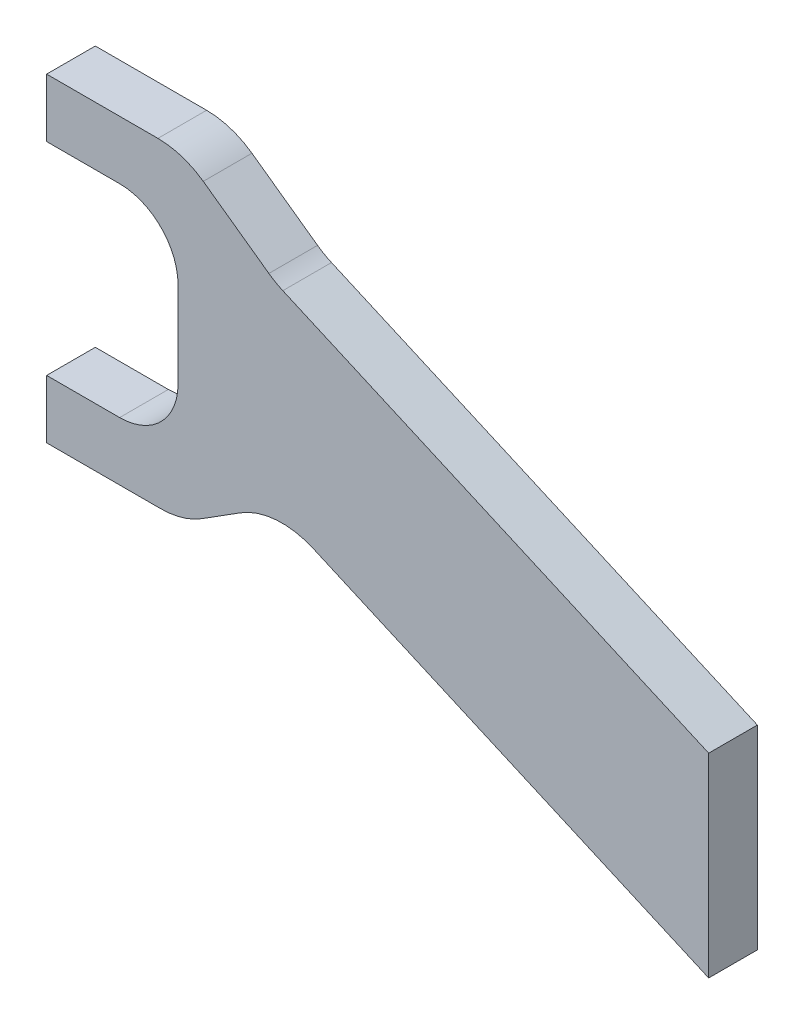
SolidWorks part; units mm, degrees
material "PBT General Purpose"
ref_plane "Front Plane" through (0, 0, 0) normal (0, 0, 1) x (1, 0, 0)
ref_plane "Top Plane" through (0, 0, 0) normal (0, 1, 0) x (1, 0, 0)
ref_plane "Right Plane" through (0, 0, 0) normal (1, 0, 0) x (0, 0, -1)
sketch "frame_outline" plane through (0, 0, 0) normal (0, 0, 1) x (1, 0, 0)
  line L89 (0, 1.64) -> (0, 1.34)
  line L99 (0, 1.34) -> (0.675, 1.34)
  line L100 (0.675, 1.34) -> (0.675, 0.3)
  line L101 (0.675, 0.3) -> (0, 0.3)
  line L102 (0, 0.3) -> (0, 0)
  line L103 (0, 0) -> (0.7, 0)
  line L104 (0.7, 0) -> (1.175, 0.3)
  line L105 (1.175, 0.3) -> (3.4, -0.68)
  line L106 (3.4, -0.68) -> (3.4, 0.32)
  line L107 (3.4, 0.32) -> (1.175, 1.3)
  line L108 (1.175, 1.3) -> (0.7, 1.64)
  line L109 (0.7, 1.64) -> (0, 1.64)
  line L110 (0.675, 0.82) -> (3.9765, 0.82) construction
  point P24 (3.4, -0.18)
  dimension "D1" = 0.3
  dimension "D2" = 0.3
  dimension "D9" = 1.64
  dimension "D10" = 0.675
  dimension "D11" = 1
  dimension "D12" = 1
  dimension "D14" = 0.7
  dimension "D15" = 0.7
  dimension "D16" = 0.5
  dimension "D3" = 3.4
extrude "Boss-Extrude1" add sketch "frame_outline" along normal mid plane 0.25
fillet "Fillet1" radius 0.3 2 edges at (0.675, 0.3, 0) (0.675, 1.34, 0)
fillet "Fillet2" radius 0.4 4 edges at (0.7, 0, 0) (1.175, 0.3, 0) (1.175, 1.3, 0) (0.7, 1.64, 0)
equation "\"t\"= 0.25'thickness of the sheets"
equation "\"t_cf\" = 0.115'thickness of single carbon fiber layer"
equation "\"t_kapton\" = 0.025'thickness of single Kapton flex layer"
equation "\"t_fr4\" = 0.1'thickness of FR4 with copper layer"
equation "\"joint_flex\"= 0.1'Width of flextures gap"
equation "\"joint_flex_eff\"= 0.02'Width of flecture after castelation"
equation "\"joint_fold\"= 0.2'Width of folding joints for 90deg fold"
equation "\"gap_tolerance\"= 0.002'Width to have interfecence fit between carbon fiber inserts"
equation "\"assemble_angle\"= 90'Angle of assembly parts"
equation "\"D1@Boss-Extrude1\"=\"t\""
equation "\"D10@frame_outline\"=\"t\"*1.5+0.3+0.1-\"joint_flex\""
equation "\"link_lift\"= 0.5'Actuation linkage amplification for the lift motion"
equation "\"link_swing\"= 0.45'Actuation linkage amplification for the swing motion"
